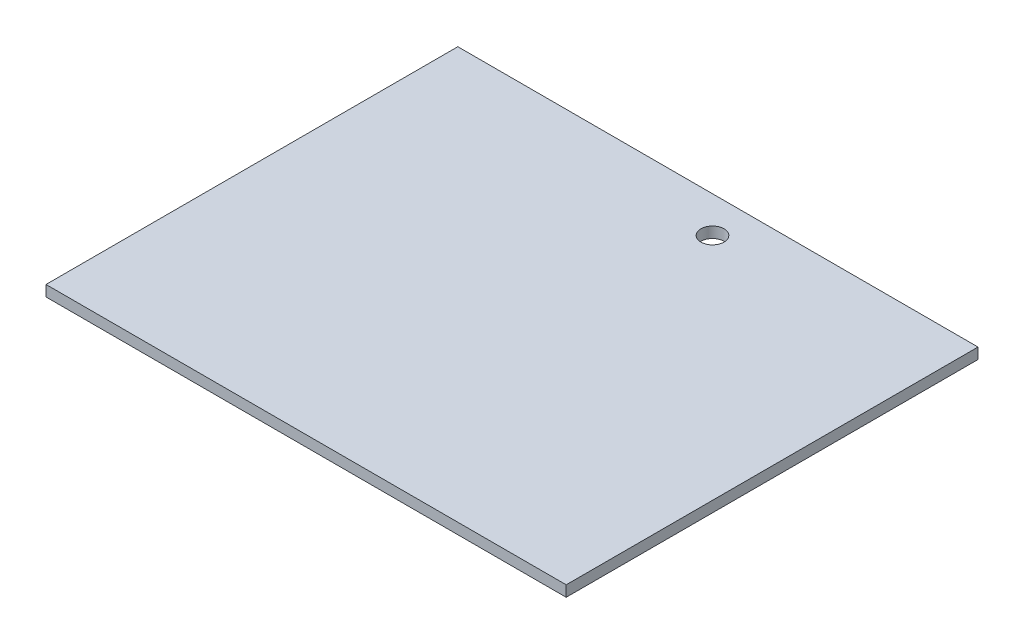
SolidWorks part; units mm, degrees
ref_plane "Front Plane" through (0, 0, 0) normal (0, 0, 1) x (1, 0, 0)
ref_plane "Top Plane" through (0, 0, 0) normal (0, 1, 0) x (1, 0, 0)
ref_plane "Right Plane" through (0, 0, 0) normal (1, 0, 0) x (0, 0, -1)
sketch "Sketch1" plane through (0, 0, 0) normal (0, 1, 0) x (1, 0, 0)
  line L0 (36, 28.5) -> (4.25, 28.5)
  line L1 (-36, 28.5) -> (36, 28.5)
  line L2 (-36, 28.5) -> (-36, -28.5)
  line L3 (-36, -28.5) -> (36, -28.5)
  line L4 (36, 28.5) -> (36, -28.5)
  line L5 (-36, 28.5) -> (36, -28.5) construction
  line L6 (-36, -28.5) -> (36, 28.5) construction
  line L7 (4.25, 28.5) -> (4.25, 23.5) construction
  circle A0 centre (4.25, 23.5) radius 1.6
  point P0 (0, 0)
  dimension "D5" = 3.2
  dimension "D1" = 72
  dimension "D2" = 57
  dimension "D3" = 31.75
  dimension "D4" = 5
extrude "Boss-Extrude1" add sketch "Sketch1" along normal blind 1.5 contours L4 L0 L1 L2 L3 A0 region at (-0.0083, 0, 0.0461)
